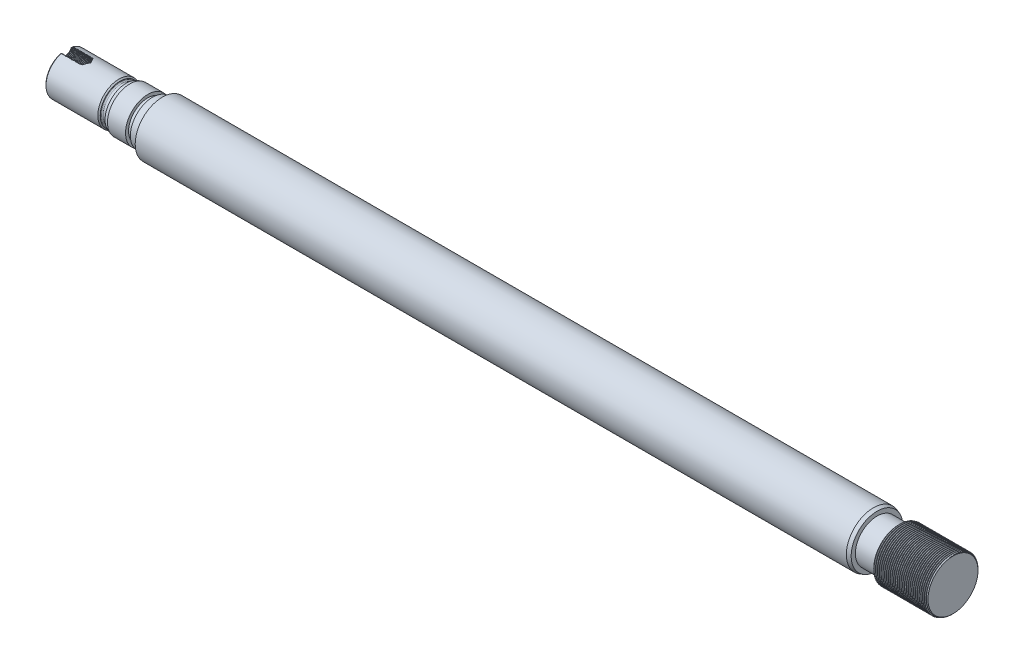
SolidWorks part; units mm, degrees
ref_plane "Front Plane" through (0, 0, 0) normal (0, 0, 1) x (1, 0, 0)
ref_plane "Top Plane" through (0, 0, 0) normal (0, 1, 0) x (1, 0, 0)
ref_plane "Right Plane" through (0, 0, 0) normal (1, 0, 0) x (0, 0, -1)
sketch "Sketch1" plane through (0, 0, 0) normal (0, 1, 0) x (1, 0, 0)
  line L0 (0, 0) -> (736, 0)
  line L1 (0, 0) -> (0, 16.5)
  line L2 (1, 17.5) -> (44, 17.5)
  line L3 (45, 16.5) -> (45, 16)
  line L5 (46, 15) -> (49, 15)
  line L6 (50, 16) -> (50, 17.5)
  line L7 (53, 18.5) -> (68, 18.5)
  line L8 (68, 18.5) -> (68, 16)
  line L9 (68, 16) -> (72, 16)
  line L10 (72, 16) -> (72, 18.5)
  line L11 (72, 18.5) -> (80, 18.5)
  line L12 (80, 18.5) -> (80, 22.5)
  line L13 (80, 22.5) -> (670, 22.5)
  line L14 (673, 21.5) -> (673, 18)
  line L15 (673, 18) -> (691, 18)
  line L16 (691, 18) -> (691, 20.75)
  line L17 (692, 21.75) -> (735, 21.75)
  line L18 (736, 20.75) -> (736, 0)
  line L19 (0, 16.5) -> (1, 17.5)
  line L20 (44, 17.5) -> (45, 16.5)
  line L21 (50, 17.5) -> (53, 18.5)
  line L22 (735, 21.75) -> (736, 20.75)
  line L23 (691, 20.75) -> (692, 21.75)
  line L24 (670, 22.5) -> (673, 21.5)
  arc A0 (49, 15) -> (50, 16) centre (49, 16) ccw
  arc A1 (45, 16) -> (46, 15) centre (46, 16) ccw
  point P4 (0, 17.5)
  point P5 (45, 17.5)
  point P9 (50, 18.5)
  point P16 (673, 22.5)
  point P19 (691, 21.75)
  point P20 (736, 21.75)
  point P35 (0, 0)
  dimension "D4" = 1
  dimension "D1" = 736
  dimension "D2" = 17.5
  dimension "D3" = 45
  dimension "D7" = 2.5
  dimension "D8" = 3.5
  dimension "D9" = 1
  dimension "D10" = 3
  dimension "D11" = 5
  dimension "D12" = 18
  dimension "D13" = 4
  dimension "D14" = 2.5
  dimension "D15" = 8
  dimension "D16" = 4
  dimension "D17" = 2.5
  dimension "D18" = 45
  dimension "D19" = 21.75
  dimension "D20" = 3.75
  dimension "D21" = 3
  dimension "D24" = 1
  dimension "D25" = 18
revolve "Revolve1" add sketch "Sketch1" angle 360 about L0
sketch "Sketch2" plane through (0, 0, 0) normal (-1, 0, 0) x (0, 0, 1)
  circle A0 centre (0, 0) radius 17.5 construction
  point P0 (0, 17.5)
hole_wizard "M10 Clearance Hole1" positions "Sketch2" profile "Sketch3" hole size "M10" standard "ISO"
sketch "Sketch3" plane through (0, 17.5, 0) normal (0, 1, 0) x (0, 0, 1)
  line L0 (0, 0) -> (0, 20.7039)
  line L1 (0, 20.7039) -> (4.5, 18)
  line L2 (4.5, 18) -> (4.5, 0)
  line L5 (4.5, 0) -> (0, 0)
  line L10 (0, 20.7039) -> (-4.5, 18) construction
  line L11 (0, -6.35) -> (0, 107.95) construction
  dimension "Hole Dia." = 9
  dimension "Hole Depth" = 18
  dimension "Drill Angle" = 118
thread "Thread1" pitch 1 start angle 0, offset 1, length 0, pitch 1, diameter 9
ref_plane "Plane1" through (-1, 17.5, -4.5) normal (0, 1, 0) x (0, 0, 1)
sketch "Thread Profile1" plane through (-1, 17.5, -4.5) normal (0, 1, 0) x (0, 0, 1)
  line L0 (0, 0) -> (0, 1) construction
  line L11 (0, 0) -> (0, 0.875)
  line L12 (0, 0.875) -> (-0.5413, 0.5625)
  line L13 (-0.5413, 0.5625) -> (-0.5413, 0.3125)
  line L15 (-0.5413, 0.3125) -> (0, 0)
  line L17 (-0.5413, 0.4375) -> (0, 0.4375) construction
  point P2 (0, 0)
  dimension "Pitch" = 1
  dimension "Profile_Angle" = 60
  dimension "Profile_Land" = 0.25
  dimension "Profile_Height" = 0.5413
thread "Thread2" pitch 1.5 profile "Thread Profile2" start angle 0, offset 2, length 0, pitch 1.5, diameter 43.5
ref_plane "Plane2" through (737, 0, 21.75) normal (0, -1, 0) x (0, 0, 1)
sketch "Thread Profile2" plane through (737, 0, 21.75) normal (0, -1, 0) x (0, 0, 1)
  line L0 (0, 0) -> (0, 1.5) construction
  line L11 (0, 0) -> (0, 1.3125)
  line L12 (0, 1.3125) -> (-0.8119, 0.8437)
  line L13 (-0.8119, 0.8437) -> (-0.8119, 0.4687)
  line L15 (-0.8119, 0.4687) -> (0, 0)
  line L17 (-0.8119, 0.6562) -> (0, 0.6562) construction
  point P2 (0, 0)
  dimension "Pitch" = 1.5
  dimension "Profile_Angle" = 60
  dimension "Profile_Land" = 0.375
  dimension "Profile_Height" = 0.8119
